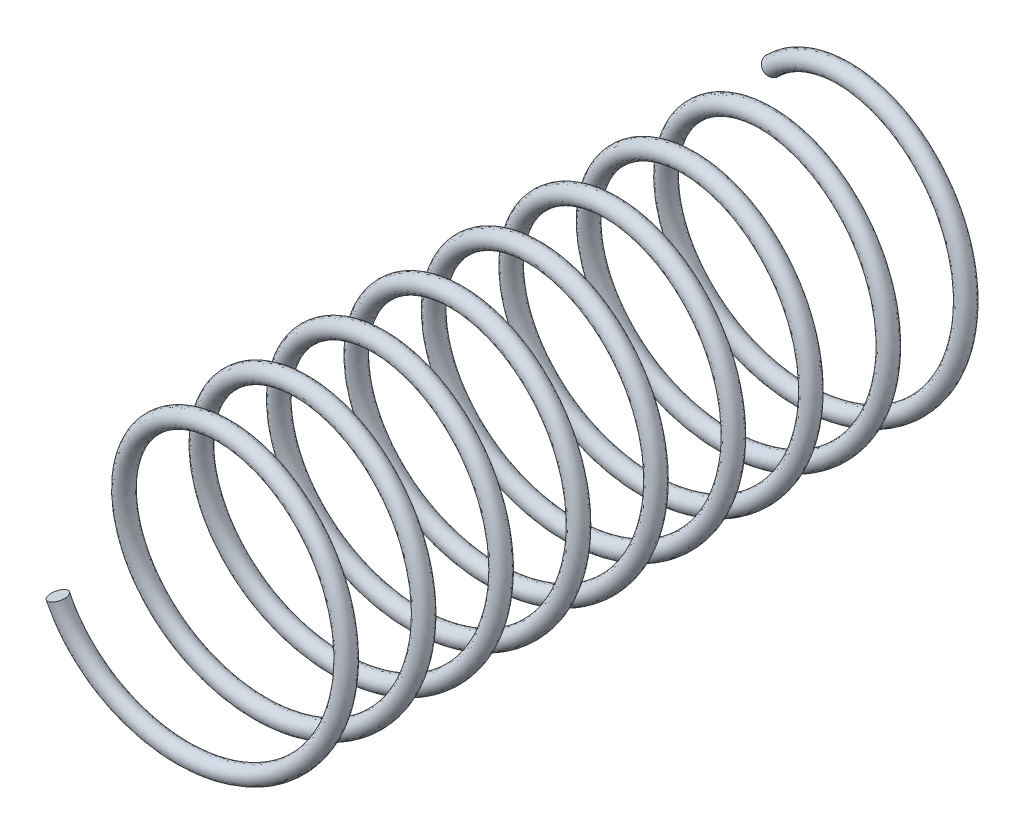
SolidWorks part; units mm, degrees
ref_plane "Front Plane" through (0, 0, 0) normal (0, 0, 1) x (1, 0, 0)
ref_plane "Top Plane" through (0, 0, 0) normal (0, 1, 0) x (1, 0, 0)
ref_plane "Right Plane" through (0, 0, 0) normal (1, 0, 0) x (0, 0, -1)
sketch "Sketch1" plane through (0, 0, 0) normal (0, 0, 1) x (1, 0, 0)
  circle A0 centre (0, 0) radius 7.239
  dimension "D1" = 14.478
curve "Helix/Spiral1" pitch 4.318 height 38.1 turns 8.8235
sweep "Sweep1" add path "Helix/Spiral1" circular profile diameter 0.9779 parameters "D3"=0.9779
